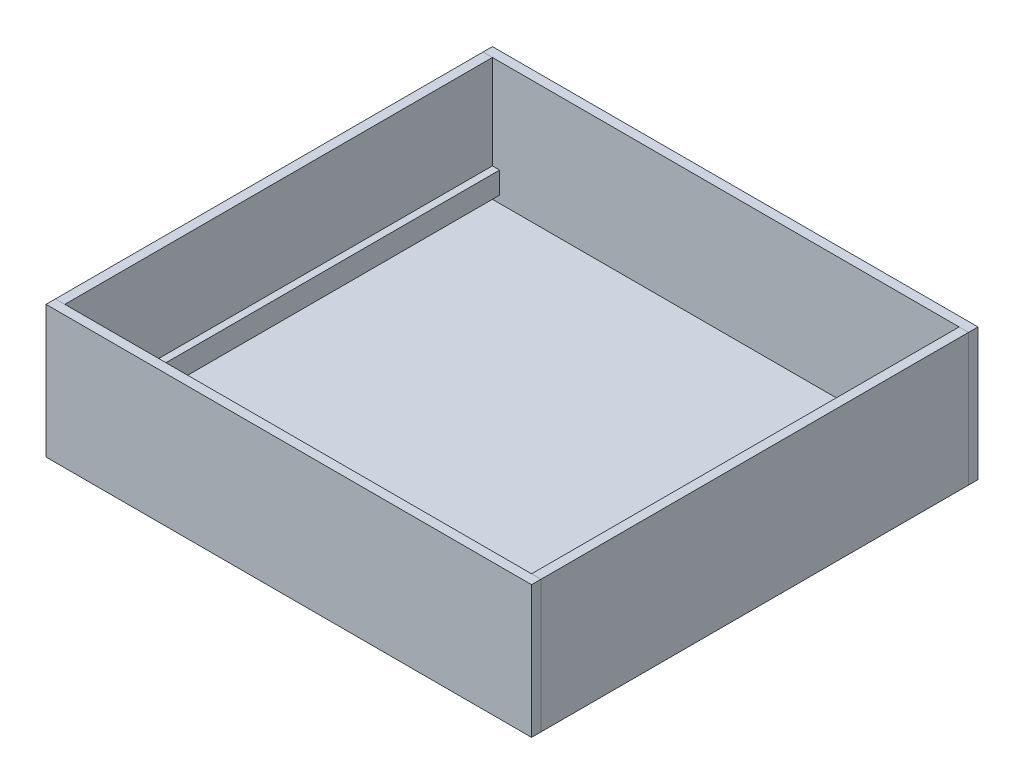
SolidWorks part; units mm, degrees
ref_plane "Front" through (0, 0, 0) normal (0, 0, 1) x (1, 0, 0)
ref_plane "Top" through (0, 0, 0) normal (0, 1, 0) x (1, 0, 0)
ref_plane "Right" through (0, 0, 0) normal (1, 0, 0) x (0, 0, -1)
sketch "Sketch1" plane through (0, 0, 0) normal (0, 0, 1) x (1, 0, 0)
  line L0 (-425.45, 0) -> (425.45, 0)
  line L1 (-425.45, 0) -> (-425.45, 231.775)
  line L2 (-425.45, 231.775) -> (-408.94, 231.775)
  line L3 (-408.94, 231.775) -> (-408.94, 0)
  line L4 (-408.94, 16.51) -> (408.94, 16.51)
  line L5 (408.94, 0) -> (408.94, 231.775)
  line L6 (408.94, 231.775) -> (425.45, 231.775)
  line L7 (425.45, 231.775) -> (425.45, 0)
  dimension "D1" = 16.51
  dimension "D2" = 850.9
  dimension "D3" = 231.775
  dimension "D4" = 16.51
extrude "Boss-Extrude1" add sketch "Sketch1" against normal blind 749.3 contours L3 L2 L1 | L5 L7 L6 region at (-417.195, 115.8875, 0) region at (417.195, 115.8875, 0)
extrude "Boss-Extrude2" add sketch "Sketch1<3>" against normal up to surface (749.3 mm away) separate body contours L4 L1 L0 L7 region at (0, 8.255, 0) up to face at (-417.195, 115.8875, -749.3)
sketch "Sketch1<3>" plane through (0, 0, 0) normal (0, 0, 1) x (1, 0, 0) same geometry as "Sketch1"
sketch "Sketch2" plane through (0, 0, -749.3) normal (0, 0, -1) x (-1, 0, 0)
  line L0 (425.45, 231.775) -> (408.94, 231.775) construction
  line L1 (-425.45, 231.775) -> (425.45, 231.775)
  line L2 (-425.45, 231.775) -> (-425.45, 0)
  line L3 (-425.45, 0) -> (425.45, 0)
  line L4 (425.45, 231.775) -> (425.45, 0)
  line L5 (425.45, 0) -> (425.45, 231.775) construction
extrude "Boss-Extrude3" add sketch "Sketch2" along normal blind 16.51 separate body
sketch "Sketch3" plane through (0, 0, 0) normal (0, 0, 1) x (1, 0, 0)
  line L0 (-408.94, 231.775) -> (-408.94, 0) construction
  line L1 (-408.94, 29.21) -> (-396.24, 29.21)
  line L2 (-408.94, 29.21) -> (-408.94, 67.31)
  line L3 (-408.94, 67.31) -> (-396.24, 67.31)
  line L4 (-396.24, 29.21) -> (-396.24, 67.31)
  line L12 (-408.94, 16.51) -> (408.94, 16.51) construction
  dimension "D1" = 12.7
  dimension "D2" = 12.7
  dimension "D3" = 38.1
extrude "Boss-Extrude4" add sketch "Sketch3" against normal up to surface (749.3 mm away) separate body up to face at (0, 115.8875, -749.3)
mirror "Mirror1" about plane through (0, 0, 0) normal (1, 0, 0) of bodies 111 113
sketch "Sketch7" plane through (0, 0, 0) normal (0, 0, 1) x (1, 0, 0)
  line L0 (-425.45, 231.775) -> (-408.94, 231.775) construction
  line L1 (-425.45, 0) -> (-425.45, 231.775) construction
  line L2 (0, 0) -> (0, 411.8049) construction
  circle A0 centre (-415.925, 200.025) radius 3.7703
  circle A1 centre (415.925, 200.025) radius 3.7703
  dimension "D1" = 7.5406
  dimension "D2" = 31.75
  dimension "D3" = 9.525
extrude "Cut-Extrude2" cut sketch "Sketch7" against normal blind 12.7
sketch "Sketch15" plane through (0, 0, 0) normal (0, 0, 1) x (1, 0, 0)
  line L1 (-425.45, 231.775) -> (425.45, 231.775)
  line L2 (-425.45, 231.775) -> (-425.45, 0)
  line L3 (-425.45, 0) -> (425.45, 0)
  line L4 (425.45, 231.775) -> (425.45, 0)
extrude "Boss-Extrude11" add sketch "Sketch15" along normal blind 16.51 separate body
sketch "Sketch13" plane through (0, 231.775, 0) normal (0, 1, 0) x (1, 0, 0)
  line L1 (-444.5, 784.86) -> (-355.6, 784.86)
  line L2 (-444.5, 784.86) -> (-444.5, 695.96)
  line L3 (-444.5, 695.96) -> (-425.45, 695.96)
  line L4 (-355.6, 784.86) -> (-355.6, 765.81)
  line L5 (-425.45, 749.3) -> (-425.45, 0) construction
  line L6 (-425.45, 765.81) -> (-355.6, 765.81)
  line L7 (-425.45, 765.81) -> (-425.45, 695.96)
  line L9 (-425.45, 765.81) -> (425.45, 765.81) construction
  dimension "D1" = 88.9
  dimension "D2" = 88.9
  dimension "D3" = 19.05
  dimension "D4" = 19.05
extrude "LEG" [suppressed] add sketch "Sketch13" against normal blind 1016 separate body
ref_plane "Plane1" [suppressed] through (0, 0, -374.65) normal (0, 0, 1) x (1, 0, 0)
mirror "Mirror3" [suppressed] about plane through (0, 0, 0) normal (1, 0, 0) of bodies 135
mirror "Mirror5" [suppressed] about plane through (0, 0, -374.65) normal (0, 0, 1) of bodies 142 135
